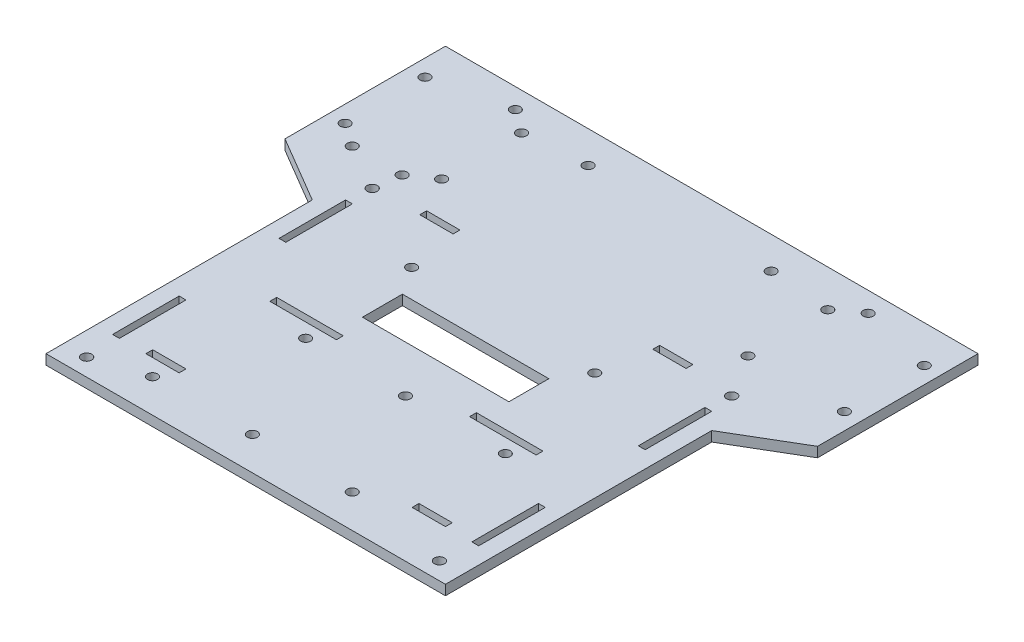
SolidWorks part; units mm, degrees
ref_plane "Front Plane" through (0, 0, 0) normal (0, 0, 1) x (1, 0, 0)
ref_plane "Top Plane" through (0, 0, 0) normal (0, 1, 0) x (1, 0, 0)
ref_plane "Right Plane" through (0, 0, 0) normal (1, 0, 0) x (0, 0, -1)
sketch "Sketch1" plane through (0, 0, 0) normal (0, 1, 0) x (1, 0, 0)
  line L0 (-60, 10) -> (-80, 21.7918)
  line L1 (60, -70) -> (-60, -70)
  line L2 (60, -70) -> (60, 70)
  line L3 (60, 70) -> (-60, 70)
  line L4 (-60, -70) -> (-60, 70)
  line L5 (60, -70) -> (-60, 70) construction
  line L6 (60, 70) -> (-60, -70) construction
  line L7 (-80, 21.7918) -> (-80, 70)
  line L8 (-80, 70) -> (-60, 70)
  line L9 (0, 0) -> (0, 70) construction
  line L10 (60, 10) -> (80, 21.7918)
  line L11 (80, 70) -> (60, 70)
  line L12 (80, 21.7918) -> (80, 70)
  point P0 (0, 0)
  dimension "D1" = 140
  dimension "D2" = 120
  dimension "D3" = 20
  dimension "D4" = 30.523
  dimension "D5" = 60
extrude "Boss-Extrude1" add sketch "Sketch1" along normal blind 3 contours L4 L1 L2 L3 | L8 L7 L0 L4 | L10 L12 L11 L2 region at (0, 0, 0) region at (-69.6368, 0, -42.8409) region at (69.6368, 0, -42.8409)
sketch "Sketch2" plane through (0, 3, 0) normal (0, 1, 0) x (1, 0, 0)
  line L2 (0, 0) -> (0, -70) construction
  line L3 (60, -70) -> (-60, -70) construction
  circle A0 centre (-38, -60) radius 1.5
  circle A1 centre (-25, -27) radius 1.5
  circle A2 centre (5, -27) radius 1.5
  circle A3 centre (-8, -60) radius 1.5
  circle A4 centre (35, -27) radius 1.5
  circle A5 centre (22, -60) radius 1.5
  dimension "D1" = 3
  dimension "D2" = 38
  dimension "D3" = 10
  dimension "D4" = 3
  dimension "D6" = 33
  dimension "D5" = 13
  dimension "D7" = 3
extrude "Cut-Extrude1" cut sketch "Sketch2" against normal through all
sketch "Sketch3" plane through (0, 3, 0) normal (0, 1, 0) x (1, 0, 0)
  line L0 (-0.0296, 57.8856) -> (-0.0296, -0.1144) construction
  line L1 (-30.0296, 33.8856) -> (29.9704, 33.8856) construction
  line L4 (-80, 21.7918) -> (-80, 70) construction
  line L6 (-80, 21.7918) -> (-80, 70) construction
  line L7 (80, 70) -> (-80, 70) construction
  line L8 (-60, 10) -> (-60, 70) construction
  line L9 (60, 10) -> (60, 70) construction
  circle A0 centre (-27.5296, 60.3856) radius 1.5
  circle A1 centre (-27.5296, 7.3856) radius 1.5
  circle A2 centre (27.4704, 7.3856) radius 1.5
  circle A3 centre (27.4704, 60.3856) radius 1.5
  point P16 (-80, 45.8959)
  dimension "D1" = 52.4704
  dimension "D2" = 36.1144
  dimension "D3" = 3
  dimension "D4" = 79.9704
  dimension "D5" = 26.5
extrude "Cut-Extrude3" cut sketch "Sketch3" against normal through all
sketch "Sketch4" plane through (0, 3, 0) normal (0, 1, 0) x (1, 0, 0)
  line L0 (-60.5, 58.8639) -> (-60.5, 32.8639) construction
  line L1 (-80, 21.7918) -> (-80, 70) construction
  line L2 (80, 70) -> (-80, 70) construction
  line L3 (0, 0) -> (0, 70) construction
  circle A0 centre (-75, 34.8639) radius 1.5
  circle A1 centre (-75, 58.8639) radius 1.5
  circle A2 centre (-46, 34.8639) radius 1.5
  circle A3 centre (-46, 58.8639) radius 1.5
  circle A4 centre (46, 58.8639) radius 1.5
  circle A5 centre (46, 34.8639) radius 1.5
  circle A6 centre (75, 34.8639) radius 1.5
  circle A7 centre (75, 58.8639) radius 1.5
  dimension "D1" = 3
  dimension "D2" = 3
  dimension "D5" = 5
  dimension "D6" = 11.1361
  dimension "D7" = 5
  dimension "D3" = 24
  dimension "D4" = 14.5
extrude "Cut-Extrude4" cut sketch "Sketch4" against normal through all
sketch "Sketch5" plane through (0, 3, 0) normal (0, 1, 0) x (1, 0, 0)
  line L0 (80, 70) -> (-80, 70) construction
  line L1 (-80, 21.7918) -> (-80, 70) construction
  circle A0 centre (-68, 30) radius 1.5
  circle A1 centre (-53, 30) radius 1.5
  dimension "D1" = 3
  dimension "D2" = 3
  dimension "D3" = 40
  dimension "D4" = 40
  dimension "D6" = 12
  dimension "D5" = 15
extrude "Cut-Extrude5" cut sketch "Sketch5" against normal blind 3
sketch "Sketch6" plane through (0, 3, 0) normal (0, 1, 0) x (1, 0, 0)
  line L0 (60, -70) -> (-60, -70) construction
  line L1 (-45, -52.95) -> (-35, -52.95)
  line L2 (-45, -52.95) -> (-45, -55)
  line L3 (-45, -55) -> (-35, -55)
  line L4 (-35, -52.95) -> (-35, -55)
  line L5 (-45, -52.95) -> (-35, -55) construction
  line L6 (-45, -55) -> (-35, -52.95) construction
  line L7 (-60, -70) -> (-60, 10) construction
  line L8 (0, 0) -> (0, -70) construction
  line L9 (35, -52.95) -> (35, -55)
  line L10 (45, -55) -> (35, -55)
  line L11 (45, -52.95) -> (45, -55)
  line L12 (45, -52.95) -> (35, -52.95)
  line L13 (20, -22.75) -> (20, -20.7)
  line L14 (-20, -22.75) -> (-40, -22.75)
  line L15 (-20, -22.75) -> (-20, -20.7)
  line L16 (-20, -20.7) -> (-40, -20.7)
  line L17 (-40, -22.75) -> (-40, -20.7)
  line L18 (-20, -22.75) -> (-40, -20.7) construction
  line L19 (-20, -20.7) -> (-40, -22.75) construction
  line L20 (20, -22.75) -> (40, -22.75)
  line L21 (40, -22.75) -> (40, -20.7)
  line L22 (20, -20.7) -> (40, -20.7)
  line L23 (-60, -30) -> (60, -30) construction
  line L24 (60, -70) -> (60, 10) construction
  line L25 (-30, -21.725) -> (60, -21.725) construction
  line L26 (30, 24.35) -> (30, 22.3)
  line L27 (-40, 24.35) -> (-30, 24.35)
  line L28 (-40, 24.35) -> (-40, 22.3)
  line L29 (-40, 22.3) -> (-30, 22.3)
  line L30 (-30, 24.35) -> (-30, 22.3)
  line L31 (-40, 24.35) -> (-30, 22.3) construction
  line L32 (-40, 22.3) -> (-30, 24.35) construction
  line L33 (40, 24.35) -> (40, 22.3)
  line L34 (40, 24.35) -> (30, 24.35)
  line L35 (40, 22.3) -> (30, 22.3)
  circle A0 centre (-53, -64.8) radius 1.525
  circle A1 centre (53, -64.8) radius 1.525
  point P0 (-40, -53.975)
  point P16 (-30, -21.725)
  point P31 (-35, 23.325)
  dimension "D9" = 7
  dimension "D11" = 3.05
  dimension "D1" = 2.05
  dimension "D2" = 15
  dimension "D3" = 15
  dimension "D4" = 10
  dimension "D5" = 2.05
  dimension "D6" = 30.2
  dimension "D7" = 20
  dimension "D8" = 20
  dimension "D10" = 5.2
  dimension "D12" = 10
  dimension "D13" = 5
  dimension "D14" = 2.05
  dimension "D15" = 43
extrude "Cut-Extrude7" cut sketch "Sketch6" against normal through all
sketch "Sketch9" plane through (0, 3, 0) normal (0, 1, 0) x (1, 0, 0)
  line L0 (80, 70) -> (-80, 70) construction
  line L1 (-80, 21.7918) -> (-80, 70) construction
  line L2 (0, 0) -> (0, 70) construction
  circle A0 centre (-54, 22) radius 1.525
  circle A2 centre (54, 22) radius 1.525
  dimension "D1" = 3.05
  dimension "D2" = 48
  dimension "D3" = 26
extrude "Cut-Extrude8" cut sketch "Sketch9" against normal blind 3
sketch "Sketch10" plane through (0, 3, 0) normal (0, 1, 0) x (1, 0, 0)
  line L0 (60, -70) -> (60, 10) construction
  line L1 (22.0465, -12.9751) -> (-21.9535, -12.9751)
  line L2 (22.0465, -12.9751) -> (22.0465, -0.9751)
  line L3 (22.0465, -0.9751) -> (-21.9535, -0.9751)
  line L4 (-21.9535, -12.9751) -> (-21.9535, -0.9751)
  line L5 (22.0465, -12.9751) -> (-21.9535, -0.9751) construction
  line L6 (22.0465, -0.9751) -> (-21.9535, -12.9751) construction
  line L7 (80, 70) -> (-80, 70) construction
  point P0 (0.0465, -6.9751)
  dimension "D1" = 12
  dimension "D2" = 44
  dimension "D3" = 37.9535
  dimension "D4" = 70.9751
extrude "Cut-Extrude9" cut sketch "Sketch10" against normal blind 5
sketch "Sketch11" plane through (0, 3, 0) normal (0, 1, 0) x (1, 0, 0)
  line L0 (80, 70) -> (-80, 70) construction
  line L1 (0, 0) -> (0, 70) construction
  line L2 (-80, 21.7918) -> (-80, 70) construction
  circle A0 centre (-53, 64) radius 1.5
  circle A1 centre (53, 64) radius 1.5
  dimension "D1" = 3
  dimension "D3" = 27
  dimension "D2" = 6
extrude "Cut-Extrude10" cut sketch "Sketch11" against normal blind 5
sketch "Sketch12" plane through (0, 3, 0) normal (0, 1, 0) x (1, 0, 0)
  line L0 (80, 70) -> (-80, 70) construction
  line L1 (-55, 15) -> (-52.95, 15)
  line L2 (-55, 15) -> (-55, -5)
  line L3 (-55, -5) -> (-52.95, -5)
  line L4 (-52.95, 15) -> (-52.95, -5)
  line L5 (-55, 15) -> (-52.95, -5) construction
  line L6 (-55, -5) -> (-52.95, 15) construction
  line L7 (-52.95, -55) -> (-55, -55)
  line L8 (-52.95, -55) -> (-52.95, -35)
  line L9 (-52.95, -35) -> (-55, -35)
  line L10 (-55, -55) -> (-55, -35)
  line L11 (-52.95, -55) -> (-55, -35) construction
  line L12 (-52.95, -35) -> (-55, -55) construction
  line L13 (-60, -70) -> (-60, 10) construction
  line L14 (60, -70) -> (-60, -70) construction
  line L15 (0, 0) -> (0, -70) construction
  line L16 (52.95, -55) -> (55, -55)
  line L17 (52.95, -55) -> (52.95, -35)
  line L18 (55, -55) -> (55, -35)
  line L19 (52.95, -35) -> (55, -35)
  line L20 (52.95, 15) -> (52.95, -5)
  line L21 (55, -5) -> (52.95, -5)
  line L22 (55, 15) -> (55, -5)
  line L23 (55, 15) -> (52.95, 15)
  point P0 (-53.975, 5)
  point P5 (-53.975, -45)
  dimension "D1" = 20
  dimension "D2" = 55
  dimension "D3" = 2.05
  dimension "D4" = 5
  dimension "D5" = 2.05
  dimension "D6" = 20
  dimension "D7" = 5
  dimension "D8" = 15
extrude "Cut-Extrude11" cut sketch "Sketch12" against normal blind 10
